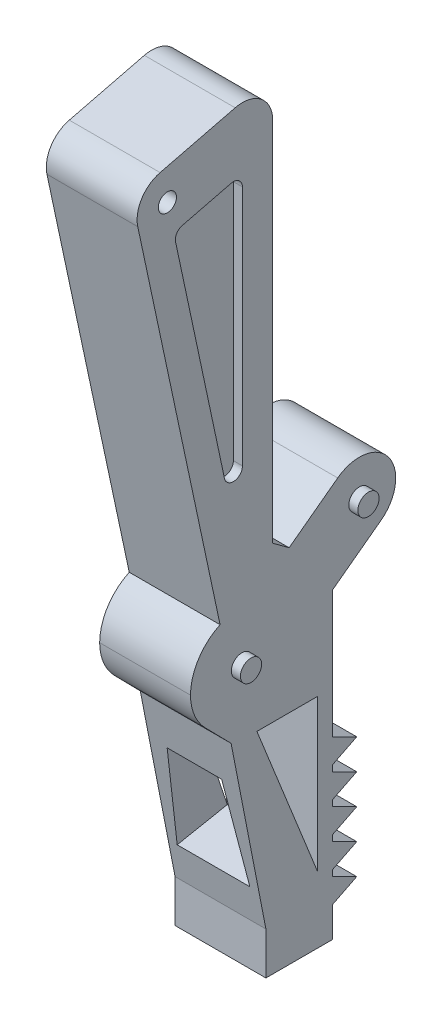
SolidWorks part; units mm, degrees
ref_plane "Front Plane" through (0, 0, 0) normal (0, 0, 1) x (1, 0, 0)
ref_plane "Top Plane" through (0, 0, 0) normal (0, 1, 0) x (1, 0, 0)
ref_plane "Right Plane" through (0, 0, 0) normal (1, 0, 0) x (0, 0, -1)
sketch "Sketch1" plane through (0, 0, 0) normal (1, 0, 0) x (0, 0, -1)
  line L0 (1.1258, 128.5472) -> (-22.1712, 122.7811)
  line L1 (-22.1712, 122.7811) -> (-7.5702, 54.3208)
  line L2 (-7.5702, 54.3208) -> (-12.4603, 53.2779)
  line L3 (-12.4603, 53.2779) -> (-12.4603, 43.2779)
  line L4 (-12.4603, 43.2779) -> (-5.7491, 36.444)
  line L5 (-5.7491, 36.444) -> (0, 7)
  line L6 (1.1258, 61.6295) -> (3.8366, 59.6273)
  line L7 (1.1258, 128.5472) -> (1.1258, 61.6295)
  line L9 (3.8366, 59.6273) -> (11.8593, 65.5968)
  line L10 (19.0228, 55.9695) -> (11, 50)
  line L11 (11, 50) -> (11, 0)
  line L12 (11, 0) -> (0, 0)
  line L13 (0, 0) -> (0, 7)
  arc A0 (11.8593, 65.5968) -> (19.0228, 55.9695) centre (15.441, 60.7832) cw
  dimension "D8" = 50
  dimension "D1" = 24
  dimension "D2" = 70
  dimension "D4" = 5
  dimension "D5" = 10
  dimension "D7" = 30
  dimension "D9" = 7
  dimension "D10" = 11
  dimension "D11" = 10
  dimension "D12" = 10
  dimension "D13" = 12
extrude "Boss-Extrude1" add sketch "Sketch1" along normal mid plane 15
sketch "Sketch2" plane through (7.5, 0, 0) normal (1, 0, 0) x (0, 0, -1)
  line L0 (11, 5) -> (15, 7)
  line L1 (11, 0) -> (11, 50) construction
  line L2 (15, 7) -> (11, 9)
  line L3 (11, 7) -> (15, 7) construction
  line L4 (11, 9) -> (11, 5)
  dimension "D1" = 4
  dimension "D2" = 4
  dimension "D3" = 2
extrude "Boss-Extrude2" add sketch "Sketch2" against normal up to surface (15 mm away) up to face at (-7.5, 53.0038, -0.2409)
pattern_linear "LPattern1" count 5 spacing 5 along (0, 1, 0) of "Boss-Extrude2"
sketch "Sketch3" plane through (7.5, 0, 0) normal (1, 0, 0) x (0, 0, -1)
  line L0 (8.5142, 11.0156) -> (8.5142, 36.0156)
  line L1 (8.5142, 36.0156) -> (-1.4858, 36.0156)
  line L2 (-1.4858, 36.0156) -> (8.5142, 11.0156)
  dimension "D1" = 10
  dimension "D2" = 25
extrude "Cut-Extrude1" cut sketch "Sketch3" against normal through all
fillet "Fillet1" radius 8.5 2 edges at (0, 43.2779, 12.4603) (0, 53.2779, 12.4603)
fillet "Fillet2" radius 5 2 edges at (0, 128.5472, -1.1258) (0, 122.7811, 22.1712)
sketch "Sketch4" plane through (7.5, 0, 0) normal (1, 0, 0) x (0, 0, -1)
  circle A0 centre (-16.2716, 119.0904) radius 1.5
  dimension "D1" = 3
extrude "Cut-Extrude2" cut sketch "Sketch4" against normal through all
sketch "Sketch5" plane through (0, 0.2571, -1.3166) normal (0, -0.1916, 0.9815) x (1, 0, 0)
  line L0 (0, 0) -> (0, 48.212) construction
  line L1 (7.5, 0) -> (-7.5, 0) construction
  line L2 (7.5, 48.212) -> (-7.5, 48.212) construction
  line L3 (4.5, 29.3703) -> (-4.5, 29.3703)
  line L4 (-4.5, 29.3703) -> (-6, 12.8586)
  line L5 (4.5, 29.3703) -> (6, 12.8586)
  line L6 (-6, 12.8586) -> (6, 12.8586)
  line L7 (7.5, 36.8703) -> (-7.5, 36.8703) construction
  line L8 (7.5, 36.8703) -> (7.5, 6.8703) construction
  point P9 (0, 29.3703)
  point P11 (0, 12.8586)
  dimension "D1" = 7.5
  dimension "D2" = 3
  dimension "D3" = 12
extrude "Cut-Extrude3" cut sketch "Sketch5" against normal up to surface (5.2916 mm away) up to face at (0, 23.5156, -3.5142)
sketch "Sketch6" plane through (7.5, 0, 0) normal (1, 0, 0) x (0, 0, -1)
  circle A0 centre (15.441, 60.7832) radius 1.75
  dimension "D1" = 3.5
extrude "Boss-Extrude3" add sketch "Sketch6" along normal blind 1.5
sketch "Sketch7" plane through (7.5, 0, 0) normal (1, 0, 0) x (0, 0, -1)
  circle A0 centre (-3.9603, 46.7537) radius 1.75
  dimension "D1" = 3.5
extrude "Boss-Extrude4" add sketch "Sketch7" along normal blind 1.5
sketch "Sketch8" plane through (7.5, 0, 0) normal (1, 0, 0) x (0, 0, -1)
  line L27 (-16.2716, 119.0904) -> (-2.6802, 55.3637)
  line L28 (-14.9253, 112.7777) -> (-6.8412, 74.8733)
  line L30 (-3.8742, 61.6295) -> (-3.8742, 122.1588)
  line L31 (-3.8742, 75.1862) -> (-3.8742, 115.0914)
  line L33 (-2.6729, 117.3053) -> (-15.0703, 114.2369)
  line L34 (-5.7345, 116.5475) -> (-13.8186, 114.5467)
  arc A0 (-3.8742, 75.1862) -> (-6.8412, 74.8733) centre (-5.3742, 75.1862) cw
  arc A1 (-3.8742, 115.0914) -> (-5.7345, 116.5475) centre (-5.3742, 115.0914) ccw
  arc A2 (-14.9253, 112.7777) -> (-13.8186, 114.5467) centre (-13.4582, 113.0906) cw
  dimension "D4" = 1.5
  dimension "D1" = 5
  dimension "D2" = 5
  dimension "D3" = 10
extrude "Cut-Extrude4" cut sketch "Sketch8" against normal blind 1.5
mirror "Mirror1" about plane through (0, 0, 0) normal (1, 0, 0) of "Cut-Extrude4", "Boss-Extrude3", "Boss-Extrude4"
